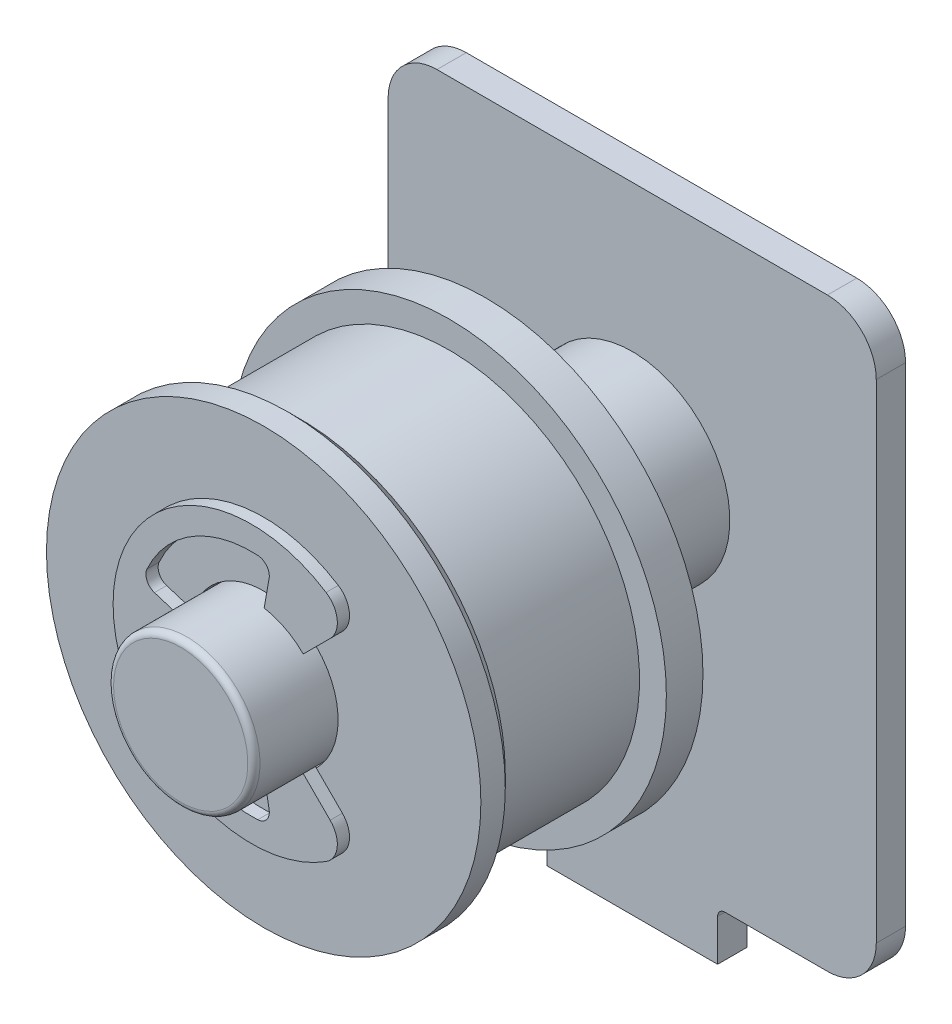
SolidWorks part; units mm, degrees
ref_plane "Plano frontal" through (0, 0, 0) normal (0, 0, 1) x (1, 0, 0)
ref_plane "Plano superior" through (0, 0, 0) normal (0, 1, 0) x (1, 0, 0)
ref_plane "Plano direito" through (0, 0, 0) normal (1, 0, 0) x (0, 0, -1)
sketch "Esboço1" plane through (0, 0, 0) normal (0, 0, 1) x (1, 0, 0)
  line L1 (48.7, 0.625) -> (-48.7, 0.625)
  line L2 (48.7, 0.625) -> (48.7, -0.625)
  line L3 (48.7, -0.625) -> (-48.7, -0.625)
  line L4 (-48.7, 0.625) -> (-48.7, -0.625)
  line L5 (48.7, 0.625) -> (-48.7, -0.625) construction
  line L6 (48.7, -0.625) -> (-48.7, 0.625) construction
  point P0 (0, 0)
  dimension "D1" = 97.4
  dimension "D2" = 1.25
extrude "Ressalto-extrusão1" add sketch "Esboço1" along normal blind 6.2
sketch "Esboço2" plane through (0, -0.625, 0) normal (0, 1, 0) x (1, 0, 0)
  line L0 (48.7, -6.2) -> (48.7, 0) construction
  line L1 (-48.7, 0) -> (48.7, 0)
  line L2 (-48.7, 0) -> (-48.7, -1.25)
  line L3 (-48.7, -1.25) -> (48.7, -1.25)
  line L4 (48.7, 0) -> (48.7, -1.25)
  dimension "D1" = 1.25
extrude "Ressalto-extrusão2" add sketch "Esboço2" along normal blind 40.6 contours L3 L4 L1 L2
fillet "Filete1" radius 1 4 edges at (48.7, 39.975, 0.625) (-48.7, 39.975, 0.625) (48.7, 0, 6.2) (-48.7, 0, 6.2)
sketch "Esboço3" plane through (0, 0, 1.25) normal (0, 0, 1) x (1, 0, 0)
  line L0 (27.7, 34.975) -> (30.7, 34.975) construction
  line L11 (39.7, 33.975) -> (43.7, 33.975)
  line L12 (39.7, 33.975) -> (39.7, 27.975)
  line L13 (39.7, 27.975) -> (43.7, 27.975)
  line L14 (43.7, 33.975) -> (43.7, 27.975)
  line L15 (39.7, 11.975) -> (43.7, 11.975)
  line L16 (39.7, 11.975) -> (39.7, 5.975)
  line L17 (39.7, 5.975) -> (43.7, 5.975)
  line L18 (43.7, 11.975) -> (43.7, 5.975)
  line L19 (-36.7, 12.975) -> (-30.7, 12.975)
  line L20 (-36.7, 12.975) -> (-36.7, 4.975)
  line L21 (-36.7, 4.975) -> (-30.7, 4.975)
  line L22 (-30.7, 12.975) -> (-30.7, 4.975)
  line L23 (27.7, 36.975) -> (30.7, 36.975)
  line L24 (27.7, 32.975) -> (30.7, 32.975)
  line L25 (0, 39.975) -> (0, 2.975) construction
  line L26 (-47.7, 39.975) -> (47.7, 39.975) construction
  line L27 (-47.7, 39.975) -> (47.7, 39.975) construction
  line L28 (-48.7, 38.975) -> (-48.7, 0.625) construction
  line L29 (-36.7, 34.975) -> (-30.7, 34.975)
  line L30 (-36.7, 34.975) -> (-36.7, 26.975)
  line L31 (-36.7, 26.975) -> (-30.7, 26.975)
  line L32 (-30.7, 34.975) -> (-30.7, 26.975)
  line L33 (48.7, 38.975) -> (48.7, 0.625) construction
  line L34 (48.7, 19.8) -> (0, 19.8) construction
  circle A5 centre (-43.7, 4.975) radius 2
  circle A6 centre (0, 4.975) radius 2
  circle A7 centre (38.95, 19.8) radius 2.5
  circle A8 centre (14.7, 19.8) radius 6
  arc A9 (27.7, 36.975) -> (27.7, 32.975) centre (27.7, 34.975) ccw
  arc A10 (30.7, 32.975) -> (30.7, 36.975) centre (30.7, 34.975) ccw
  point P22 (29.2, 34.975)
  point P33 (25.7, 34.975)
  point P34 (32.7, 34.975)
  dimension "D14" = 5
  dimension "D16" = 16
  dimension "D27" = 4
  dimension "D3" = 4
  dimension "D6" = 12
  dimension "D17" = 5
  dimension "D4" = 35
  dimension "D8" = 34
  dimension "D9" = 6
  dimension "D10" = 4
  dimension "D11" = 6
  dimension "D12" = 4
  dimension "D13" = 5
  dimension "D15" = 6
  dimension "D18" = 9.75
  dimension "D19" = 8
  dimension "D20" = 6
  dimension "D21" = 8
  dimension "D22" = 6
  dimension "D23" = 12
  dimension "D24" = 12
  dimension "D25" = 5
  dimension "D26" = 14
  dimension "D28" = 5
  dimension "D29" = 35
  dimension "D30" = 0
  dimension "D31" = 4
  dimension "D32" = 7
  dimension "D33" = 3
  dimension "D34" = 16
extrude "Corte-extrusão1" cut sketch "Esboço3" against normal blind 40.6
sketch "Esboço5" plane through (0, 0, 0) normal (0, 0, -1) x (-1, 0, 0)
  line L0 (-20.7, 19.8) -> (48.7, 19.8) construction
  line L1 (48.7, 38.975) -> (48.7, -0.625) construction
  line L2 (47.7, 39.975) -> (-47.7, 39.975) construction
  line L3 (48.7, 23.975) -> (48.7, 19.8) construction
  circle A0 centre (4.1, 23.975) radius 2
  circle A1 centre (25.7, 19.8) radius 3
  circle A2 centre (-14.7, 19.8) radius 6 construction
  dimension "D1" = 23
  dimension "6" = 6
  dimension "D2" = 4
  dimension "D3" = 16
  dimension "D4" = 44.6
sketch "Esboço6" plane through (0, 0, 0) normal (0, 0, -1) x (-1, 0, 0)
  circle A0 centre (25.7, 19.8) radius 3
  dimension "D1" = 6
extrude "Ressalto-extrusão3" add sketch "Esboço6" against normal blind 22.5
sketch "Esboço7" plane through (0, 0, 0) normal (0, 0, -1) x (-1, 0, 0)
  circle A0 centre (4.1, 23.975) radius 2.25
  dimension "D1" = 4.5
extrude "Ressalto-extrusão4" add sketch "Esboço7" against normal blind 12.3
fillet "Filete2" radius 0.25 2 edges at (-6.35, 23.975, 12.3) (-28.7, 19.8, 22.5)
sketch "Esboço12" plane through (0, 0, 0) normal (0, 0, 1) x (1, 0, 0)
  circle A0 centre (-4.1, 23.975) radius 4
  dimension "D1" = 8
extrude "Ressalto-extrusão7" add sketch "Esboço12" along normal blind 3
sketch "Esboço13" plane through (0, 0, 0) normal (0, 0, -1) x (-1, 0, 0)
  circle A0 centre (25.7, 19.8) radius 4.5
  dimension "D1" = 9
extrude "Ressalto-extrusão8" add sketch "Esboço13" against normal blind 8.1
sketch "Esboço8" plane through (0, 0, 3) normal (0, 0, 1) x (1, 0, 0)
  circle A0 centre (-4.1, 23.975) radius 16.365
  circle A1 centre (-4.1, 23.975) radius 2.3
  dimension "D1" = 32.73
  dimension "D2" = 4.6
extrude "Ressalto-extrusão5" add sketch "Esboço8" along normal blind 4
sketch "Esboço9" plane through (0, 0, 3) normal (0, 0, 1) x (1, 0, 0)
  circle A1 centre (-4.1, 23.975) radius 4
  circle A2 centre (-4.1, 23.975) radius 2.3
  dimension "D1" = 8
extrude "Ressalto-extrusão6" add sketch "Esboço9" along normal blind 8.9
sketch "Esboço10" plane through (0, 0, 7) normal (0, 0, 1) x (1, 0, 0)
  circle A0 centre (-4.1, 23.975) radius 4.9
  circle A1 centre (-4.1, 23.975) radius 13.865
  circle A2 centre (-4.1, 23.975) radius 16.365 construction
  dimension "D1" = 9.8
  dimension "D2" = 2.5
extrude "Corte-extrusão2" cut sketch "Esboço10" against normal blind 1
sketch "Esboço11" plane through (0, 0, 3) normal (0, 0, -1) x (-1, 0, 0)
  circle A1 centre (4.1, 23.975) radius 13.86
  circle A2 centre (4.1, 23.975) radius 4.9
extrude "Corte-extrusão3" cut sketch "Esboço11" against normal blind 1
sketch "Esboço14" plane through (0, 0, 8.1) normal (0, 0, 1) x (1, 0, 0)
  circle A0 centre (-25.7, 19.8) radius 18.34
  circle A1 centre (-25.7, 19.8) radius 3.1
  circle A2 centre (-25.7, 19.8) radius 3 construction
  dimension "D1" = 36.68
  dimension "D2" = 0.1
extrude "Ressalto-extrusão9" add sketch "Esboço14" along normal blind 4
sketch "Esboço15" plane through (0, 0, 8.1) normal (0, 0, 1) x (1, 0, 0)
  circle A0 centre (-25.7, 19.8) radius 7.8
  circle A1 centre (-25.7, 19.8) radius 3.1
  dimension "D1" = 15.6
extrude "Ressalto-extrusão10" add sketch "Esboço15" along normal blind 11.6
sketch "Esboço16" plane through (0, 0, 19.7) normal (0, 0, 1) x (1, 0, 0)
  circle A0 centre (-25.7, 19.8) radius 3.1
  circle A1 centre (-25.7, 19.8) radius 8.9
  dimension "D1" = 17.8
extrude "Ressalto-extrusão11" add sketch "Esboço16" against normal blind 1.5
chamfer "Chanfro1" distance 0.5 angle 45 1 edges at (-16.8, 19.8, 18.2)
sketch "Esboço17" plane through (0, 0, 19.7) normal (0, 0, 1) x (1, 0, 0)
  circle A0 centre (-25.7, 19.8) radius 3.1
  circle A1 centre (-25.7, 19.8) radius 3.5
  dimension "D1" = 7
extrude "Ressalto-extrusão12" add sketch "Esboço17" along normal blind 0.5
sketch "Esboço18" plane through (0, 0, 12.1) normal (0, 0, 1) x (1, 0, 0)
  circle A0 centre (-25.7, 19.8) radius 15.84
  circle A1 centre (-25.7, 19.8) radius 8.9
  circle A2 centre (-25.7, 19.8) radius 18.34 construction
  dimension "D1" = 2.5
  dimension "D2" = 17.8
extrude "Corte-extrusão4" cut sketch "Esboço18" against normal blind 1
sketch "Esboço19" plane through (0, 0, 8.1) normal (0, 0, -1) x (-1, 0, 0)
  circle A0 centre (25.7, 19.8) radius 8.9
  circle A1 centre (25.7, 19.8) radius 15.825
extrude "Corte-extrusão5" cut sketch "Esboço19" against normal blind 1
sketch "Esboço20" plane through (0, 0, 20.2) normal (0, 0, 1) x (1, 0, 0)
  line L0 (-28.3227, 20.6269) -> (-29.675, 21.0533)
  line L3 (-23.7555, 21.7445) -> (-22.4747, 23.0253)
  line L4 (-25.2225, 22.5082) -> (-24.9763, 23.9046)
  line L5 (-23.7555, 17.8555) -> (-22.4747, 16.5747)
  line L6 (-25.2225, 17.0918) -> (-24.9763, 15.6954)
  line L7 (-28.3227, 18.9731) -> (-29.675, 18.5467)
  arc A0 (-22.6425, 24.5746) -> (-22.6425, 15.0254) centre (-25.7, 19.8) ccw
  arc A1 (-25.4411, 24.4906) -> (-29.9802, 21.7362) centre (-25.7, 19.8) ccw
  arc A2 (-28.3227, 20.6269) -> (-28.3227, 18.9731) centre (-25.7, 19.8) ccw
  arc A3 (-23.7555, 21.7445) -> (-25.2225, 22.5082) centre (-25.7, 19.8) ccw
  arc A4 (-25.2225, 17.0918) -> (-23.7555, 17.8555) centre (-25.7, 19.8) ccw
  arc A5 (-29.9802, 17.8638) -> (-25.4411, 15.1094) centre (-25.7, 19.8) ccw
  arc A6 (-22.4747, 16.5747) -> (-22.6425, 15.0254) centre (-23.1818, 15.8675) cw
  arc A7 (-22.4747, 23.0253) -> (-22.6425, 24.5746) centre (-23.1818, 23.7325) ccw
  arc A8 (-25.4411, 15.1094) -> (-24.9763, 15.6954) centre (-25.4687, 15.6086) ccw
  arc A9 (-25.4411, 24.4906) -> (-24.9763, 23.9046) centre (-25.4687, 23.9914) cw
  arc A10 (-29.9802, 17.8638) -> (-29.675, 18.5467) centre (-29.5246, 18.0698) cw
  arc A11 (-29.9802, 21.7362) -> (-29.675, 21.0533) centre (-29.5246, 21.5302) ccw
  dimension "D2" = 1
  dimension "D3" = 0.5
  dimension "D1" = 35
  dimension "D4" = 35
  dimension "D5" = 35
extrude "Ressalto-extrusão13" add sketch "Esboço20" along normal blind 0.5
sketch "Esboço21" plane through (0, 0, 0) normal (0, 0, -1) x (-1, 0, 0)
  line L0 (-29.3939, 34.975) -> (0, 4.975) construction
  line L1 (3.3061, 4.975) -> (-3.6939, 4.975) construction
  line L2 (3.5952, 5.1615) -> (2.7796, 20.8817)
  line L3 (-13.4337, 37.4293) -> (-29.134, 38.5656)
  line L4 (0, 1.375) -> (-4.8727, 1.375)
  line L5 (-32.9939, 34.975) -> (-32.9939, 30.076)
  line L6 (-32.9939, 30.076) -> (-30.4878, 27.5182)
  line L7 (-7.4776, 4.0335) -> (-4.8727, 1.375)
  circle A2 centre (0, 4.975) radius 1.75
  circle A3 centre (-29.3939, 34.975) radius 1.75
  arc A4 (-30.4878, 27.5182) -> (-7.4776, 4.0335) centre (-14.6969, 19.975) ccw
  arc A5 (0, 1.375) -> (3.5952, 5.1615) centre (0, 4.975) ccw
  arc A7 (-29.134, 38.5656) -> (-32.9939, 34.975) centre (-29.3939, 34.975) ccw
  arc A9 (2.7796, 20.8817) -> (-13.4337, 37.4293) centre (-14.6969, 19.975) ccw
  dimension "D2" = 3.5
  dimension "D3" = 3.5
  dimension "D4" = 35
  dimension "D5" = 7.2
  dimension "D1" = 42
  dimension "D7" = 6
extrude "Ressalto-extrusão14" add sketch "Esboço21" along normal blind 0.92
sketch "Esboço23" plane through (0, 0, 0) normal (0, 0, 1) x (1, 0, 0)
  circle A0 centre (14.7, 19.8) radius 17.675
extrude "Ressalto-extrusão15" add sketch "Esboço23" against normal blind 15
fillet "Filete4" radius 1 1 edges at (32.375, 19.8, -15)
sketch "Esboço24" plane through (0, 0, -0.92) normal (0, 0, -1) x (-1, 0, 0)
  circle A0 centre (0, 4.975) radius 1.75
  circle A1 centre (0, 4.975) radius 2.05
  circle A2 centre (-29.3939, 34.975) radius 1.75
  circle A3 centre (-29.3939, 34.975) radius 2.05
  dimension "D1" = 0.3
  dimension "D2" = 0.3
extrude "Ressalto-extrusão16" add sketch "Esboço24" along normal blind 1
sketch "Esboço25" plane through (0, 0, -15) normal (0, 0, -1) x (-1, 0, 0)
  circle A0 centre (-14.7, 19.8) radius 2.5
  dimension "D1" = 5
extrude "Ressalto-extrusão17" add sketch "Esboço25" along normal blind 0.1
sketch "Esboço26" plane through (0, 0, -15.1) normal (0, 0, -1) x (-1, 0, 0)
  circle A0 centre (-14.7, 19.8) radius 1
  dimension "D1" = 2
extrude "Ressalto-extrusão18" add sketch "Esboço26" along normal blind 0.5
fillet "Filete6" radius 0.1 1 edges at (12.2, 19.8, -15.1)
sketch "Esboço27" plane through (0, 0, -15) normal (0, 0, 1) x (1, 0, 0)
  circle A0 centre (14.7, 19.8) radius 4.99
  dimension "D1" = 9.98
extrude "Ressalto-extrusão19" add sketch "Esboço27" along normal blind 16.57
sketch "Esboço28" plane through (0, 0, -15.6) normal (0, 0, -1) x (-1, 0, 0)
  circle A0 centre (-14.7, 19.8) radius 1
extrude "Ressalto-extrusão20" add sketch "Esboço28" against normal blind 25
fillet "Filete5" radius 0.25 2 edges at (13.7, 19.8, -15.6) (13.7, 19.8, 9.4)
ref_plane "Plano2" through (0, 0, 9.15) normal (0, 0, 1) x (1, 0, 0)
sketch "Esboço29" plane through (0, 0, 9.15) normal (0, 0, 1) x (1, 0, 0)
  circle A0 centre (14.7, 19.8) radius 3.59
  dimension "D1" = 7.18
extrude "Ressalto-extrusão21" add sketch "Esboço29" against normal blind 6
sketch "Esboço30" plane through (0, 0, 1.25) normal (0, 0, 1) x (1, 0, 0)
  circle A0 centre (0, 4.975) radius 2.7
  circle A1 centre (29.3939, 34.975) radius 2.7
  dimension "D1" = 5.4
  dimension "D2" = 5.4
extrude "Ressalto-extrusão22" add sketch "Esboço30" along normal blind 2
fillet "Filete7" radius 1.4 2 edges at (2.7, 4.975, 3.25) (32.0939, 34.975, 3.25)
sketch "Esboço31" plane through (0, 0, 3.25) normal (0, 0, 1) x (1, 0, 0)
  line L1 (29.0939, 37.175) -> (29.6939, 37.175)
  line L2 (28.8939, 36.975) -> (28.8939, 35.975)
  line L3 (29.0939, 32.775) -> (29.6939, 32.775)
  line L4 (29.8939, 36.975) -> (29.8939, 35.975)
  line L7 (31.3939, 35.475) -> (30.3939, 35.475)
  line L8 (31.5939, 35.275) -> (31.5939, 34.675)
  line L9 (31.3939, 34.475) -> (30.3939, 34.475)
  line L10 (27.1939, 35.275) -> (27.1939, 34.675)
  line L15 (28.8939, 33.975) -> (28.8939, 32.975)
  line L17 (29.8939, 33.975) -> (29.8939, 32.975)
  line L18 (28.3939, 35.475) -> (27.3939, 35.475)
  line L19 (28.3939, 34.475) -> (27.3939, 34.475)
  line L42 (-0.1421, 7.325) -> (0.4579, 7.325)
  line L43 (-0.3421, 7.125) -> (-0.3421, 6.125)
  line L44 (-0.1421, 2.925) -> (0.4579, 2.925)
  line L45 (0.6579, 7.125) -> (0.6579, 6.125)
  line L46 (2.1579, 5.625) -> (1.1579, 5.625)
  line L47 (2.3579, 5.425) -> (2.3579, 4.825)
  line L48 (2.1579, 4.625) -> (1.1579, 4.625)
  line L49 (-2.0421, 5.425) -> (-2.0421, 4.825)
  line L50 (-0.3421, 4.125) -> (-0.3421, 3.125)
  line L51 (0.6579, 4.125) -> (0.6579, 3.125)
  line L52 (-0.8421, 5.625) -> (-1.8421, 5.625)
  line L53 (-0.8421, 4.625) -> (-1.8421, 4.625)
  arc A0 (29.8939, 33.975) -> (30.3939, 34.475) centre (30.3939, 33.975) cw
  arc A1 (28.8939, 33.975) -> (28.3939, 34.475) centre (28.3939, 33.975) ccw
  arc A2 (29.8939, 35.975) -> (30.3939, 35.475) centre (30.3939, 35.975) ccw
  arc A3 (28.8939, 35.975) -> (28.3939, 35.475) centre (28.3939, 35.975) cw
  arc A4 (28.8939, 32.975) -> (29.0939, 32.775) centre (29.0939, 32.975) ccw
  arc A5 (29.6939, 32.775) -> (29.8939, 32.975) centre (29.6939, 32.975) ccw
  arc A6 (31.5939, 34.675) -> (31.3939, 34.475) centre (31.3939, 34.675) cw
  arc A7 (31.3939, 35.475) -> (31.5939, 35.275) centre (31.3939, 35.275) cw
  arc A8 (29.6939, 37.175) -> (29.8939, 36.975) centre (29.6939, 36.975) cw
  arc A9 (29.0939, 37.175) -> (28.8939, 36.975) centre (29.0939, 36.975) ccw
  arc A10 (27.3939, 35.475) -> (27.1939, 35.275) centre (27.3939, 35.275) ccw
  arc A11 (27.3939, 34.475) -> (27.1939, 34.675) centre (27.3939, 34.675) cw
  circle A24 centre (29.3939, 34.975) radius 1.3 construction
  arc A37 (0.6579, 4.125) -> (1.1579, 4.625) centre (1.1579, 4.125) cw
  arc A38 (-0.3421, 4.125) -> (-0.8421, 4.625) centre (-0.8421, 4.125) ccw
  arc A39 (0.6579, 6.125) -> (1.1579, 5.625) centre (1.1579, 6.125) ccw
  arc A40 (-0.3421, 6.125) -> (-0.8421, 5.625) centre (-0.8421, 6.125) cw
  arc A41 (-0.3421, 3.125) -> (-0.1421, 2.925) centre (-0.1421, 3.125) ccw
  arc A42 (0.4579, 2.925) -> (0.6579, 3.125) centre (0.4579, 3.125) ccw
  arc A43 (2.3579, 4.825) -> (2.1579, 4.625) centre (2.1579, 4.825) cw
  arc A44 (2.1579, 5.625) -> (2.3579, 5.425) centre (2.1579, 5.425) cw
  arc A45 (0.4579, 7.325) -> (0.6579, 7.125) centre (0.4579, 7.125) cw
  arc A46 (-0.1421, 7.325) -> (-0.3421, 7.125) centre (-0.1421, 7.125) ccw
  arc A47 (-1.8421, 5.625) -> (-2.0421, 5.425) centre (-1.8421, 5.425) ccw
  arc A48 (-1.8421, 4.625) -> (-2.0421, 4.825) centre (-1.8421, 4.825) cw
  point P0 (0, 4.975)
  point P6 (29.3939, 34.975)
  point P19 (28.8939, 34.475)
  point P24 (28.8939, 35.475)
  point P27 (28.8939, 32.775)
  point P30 (29.8939, 32.775)
  point P33 (31.5939, 34.475)
  point P36 (31.5939, 35.475)
  point P39 (29.8939, 37.175)
  point P44 (27.1939, 35.475)
  point P128 (0.1579, 5.125)
  point P133 (0.1579, 5.125)
  dimension "D5" = 0.5
  dimension "D6" = 0.2
  dimension "D9" = 0.5
  dimension "D10" = 0.2
  dimension "D1" = 4.4
  dimension "D2" = 4.4
  dimension "D3" = 1
  dimension "D4" = 1
extrude "Corte-extrusão6" cut sketch "Esboço31" against normal blind 1.4
sketch "Esboço32" plane through (0, 0, 1.25) normal (0, 0, -1) x (-1, 0, 0)
  circle A0 centre (0, 4.975) radius 1.75
  circle A1 centre (-29.3939, 34.975) radius 1.75
extrude "Ressalto-extrusão23" add sketch "Esboço32" along normal blind 7.8
chamfer "Chanfro2" distance 1 angle 25 2 edges at (-1.75, 4.975, -6.55) (27.6439, 34.975, -6.55) first distance on face at (-1.75, 4.975, -1.92) first distance on face at (27.6439, 34.975, -1.92)
sketch "Esboço33" plane through (0, 0, -0.92) normal (0, 0, -1) x (-1, 0, 0)
  line L1 (3.2243, 12.8461) -> (4.2922, 22.7889)
  line L2 (4.2922, 22.7889) -> (2.6901, 22.961)
  line L3 (3.2243, 12.8461) -> (1.6222, 13.0182)
  arc A4 (1.6222, 13.0182) -> (2.6901, 22.961) centre (-14.7, 19.8) ccw
  arc A7 (1.6222, 13.0182) -> (2.6901, 22.961) centre (-14.7, 19.8) ccw
  arc M4 (2.9127, 18.3164) -> (-7.2301, 3.781) centre (-14.7, 19.8) cw
  line M8 (3.5952, 5.1615) -> (2.9127, 18.3164)
  dimension "D1" = 10
  dimension "D2" = 90
extrude "Ressalto-extrusão24" add sketch "Esboço33" along normal blind 10 contours A4 L3 L1 L2 M8 | L3 M8 M4 region at (-3.4256, 19.3944, -0.92) region at (-2.6269, 14.5261, -0.92)
sketch "Esboço34" plane through (-1.8235, -0.1959, 0) normal (-0.9943, -0.1068, 0) x (0, 0, 1)
  line L0 (-5.92, 23.117) -> (-5.92, 13.117) construction
  line L1 (-10.92, 23.117) -> (-0.92, 23.117) construction
  line L2 (-10.92, 13.117) -> (-0.92, 13.117) construction
  circle A0 centre (-5.92, 18.117) radius 2
  dimension "D1" = 4
extrude "Ressalto-extrusão25" add sketch "Esboço34" along normal blind 5
sketch "Esboço35" plane through (0, 0, 12.1) normal (0, 0, 1) x (1, 0, 0)
  line L0 (-48.7, 38.975) -> (-48.7, 0.625) construction
  circle A0 centre (-398.7, 19.8) radius 7.8
  point P2 (-25.7, 19.8)
  dimension "D1" = 15.6
  dimension "D2" = 350
  dimension "D3" = 0
extrude "Ressalto-extrusão26" add sketch "Esboço35" along normal blind 7.6 separate body
sketch "Esboço37" plane through (0, 0, 19.7) normal (0, 0, 1) x (1, 0, 0)
  circle A0 centre (-398.7, 19.8) radius 8.9
  dimension "D1" = 17.8
extrude "Ressalto-extrusão27" add sketch "Esboço37" against normal blind 1.5
chamfer "Chanfro3" distance 0.5 angle 45 1 edges at (-389.8, 19.8, 18.2)
sketch "Esboço38" plane through (0, 0, 12.1) normal (0, 0, -1) x (-1, 0, 0)
  circle A0 centre (398.7, 19.8) radius 8.9
extrude "Ressalto-extrusão28" add sketch "Esboço38" along normal blind 1.5
sketch "Esboço39" plane through (0, 0, 19.7) normal (0, 0, 1) x (1, 0, 0)
  circle A0 centre (-398.7, 19.8) radius 3.05
  dimension "D1" = 6.1
extrude "Corte-extrusão7" cut sketch "Esboço39" against normal blind 35.5 and the other way blind 16
sketch "Esboço40" plane through (0, 0, 10.6) normal (0, 0, -1) x (-1, 0, 0)
  circle A0 centre (398.7, 19.8) radius 4
  dimension "D1" = 8
extrude "Ressalto-extrusão29" add sketch "Esboço40" along normal blind 6
sketch "Esboço41" plane through (0, 0, 4.6) normal (0, 0, -1) x (-1, 0, 0)
  circle A0 centre (398.7, 19.8) radius 3
  dimension "D1" = 6
extrude "Ressalto-extrusão30" add sketch "Esboço41" against normal blind 18.5
fillet "Filete8" radius 0.25 1 edges at (-401.7, 19.8, 23.1)
sketch "Esboço42" plane through (0, 0, 19.7) normal (0, 0, 1) x (1, 0, 0)
  line L6 (-401.3227, 20.6269) -> (-402.675, 21.0533)
  line L7 (-396.7555, 21.7445) -> (-395.4747, 23.0253)
  line L8 (-398.2225, 22.5082) -> (-397.9763, 23.9046)
  line L9 (-396.7555, 17.8555) -> (-395.4747, 16.5747)
  line L10 (-398.2225, 17.0918) -> (-397.9763, 15.6954)
  line L11 (-401.3227, 18.9731) -> (-402.675, 18.5467)
  arc A12 (-395.6425, 24.5746) -> (-395.6425, 15.0254) centre (-398.7, 19.8) ccw
  arc A13 (-398.4411, 24.4906) -> (-402.9802, 21.7362) centre (-398.7, 19.8) ccw
  arc A14 (-401.3227, 20.6269) -> (-401.3227, 18.9731) centre (-398.7, 19.8) ccw
  arc A15 (-396.7555, 21.7445) -> (-398.2225, 22.5082) centre (-398.7, 19.8) ccw
  arc A16 (-398.2225, 17.0918) -> (-396.7555, 17.8555) centre (-398.7, 19.8) ccw
  arc A17 (-402.9802, 17.8638) -> (-398.4411, 15.1094) centre (-398.7, 19.8) ccw
  arc A18 (-395.4747, 16.5747) -> (-395.6425, 15.0254) centre (-396.1818, 15.8675) cw
  arc A19 (-395.4747, 23.0253) -> (-395.6425, 24.5746) centre (-396.1818, 23.7325) ccw
  arc A20 (-398.4411, 15.1094) -> (-397.9763, 15.6954) centre (-398.4687, 15.6086) ccw
  arc A21 (-398.4411, 24.4906) -> (-397.9763, 23.9046) centre (-398.4687, 23.9914) cw
  arc A22 (-402.9802, 17.8638) -> (-402.675, 18.5467) centre (-402.5246, 18.0698) cw
  arc A23 (-402.9802, 21.7362) -> (-402.675, 21.0533) centre (-402.5246, 21.5302) ccw
  point P0 (-398.7, 19.8)
  dimension "D4" = 1
  dimension "D5" = 0.5
  dimension "D1" = 35
  dimension "D2" = 35
  dimension "D3" = 35
extrude "Ressalto-extrusão31" add sketch "Esboço42" along normal blind 0.5
sketch "Esboço43" plane through (0, 0, 4.6) normal (0, 0, -1) x (-1, 0, 0)
  line L0 (402.2, 5.8) -> (402.2, 3.8)
  line L1 (408.7, 29.8) -> (388.7, 29.8)
  line L2 (408.7, 29.8) -> (408.7, 5.8)
  line L3 (408.7, 5.8) -> (402.2, 5.8)
  line L4 (388.7, 29.8) -> (388.7, 5.8)
  line L5 (395.2, 5.8) -> (388.7, 5.8)
  line L6 (408.7, 19.8) -> (388.7, 19.8) construction
  line L9 (395.2, 3.8) -> (402.2, 3.8)
  line L11 (398.7, 29.8) -> (398.7, 19.8) construction
  line L14 (395.2, 5.8) -> (395.2, 3.8)
  point P0 (398.7, 19.8)
  dimension "D1" = 20
  dimension "D2" = 24
  dimension "D4" = 7
  dimension "D5" = 26
extrude "Ressalto-extrusão32" add sketch "Esboço43" along normal blind 1.2 contours L1 L4 L5 L14 L9 L0 L3 L2
fillet "Filete9" radius 2 4 edges at (-408.7, 5.8, 4) (-388.7, 5.8, 4) (-388.7, 29.8, 4) (-408.7, 29.8, 4)
fillet "Filete10" radius 0.3 2 edges at (-402.2, 5.8, 4) (-395.2, 5.8, 4)
ref_plane "Plano3" through (0, 0, 13.1) normal (0, 0, 1) x (1, 0, 0)
sketch "Esboço45" plane through (0, 0, 3.4) normal (0, 0, -1) x (-1, 0, 0)
  line L0 (398.7, 3.8) -> (398.7, 29.8) construction
  line L1 (395.2, 3.8) -> (402.2, 3.8) construction
  line L2 (406.7, 29.8) -> (390.7, 29.8) construction
  line L4 (388.7, 27.8) -> (388.7, 7.8) construction
  line L5 (388.7, 17.8) -> (408.7, 17.8) construction
  line L6 (408.7, 27.8) -> (408.7, 7.8) construction
fillet "Filete11" radius 0.5 1 edges at (0, -0.625, 0)
fillet "Filete12" radius 0.25 1 edges at (0, 0.625, 1.25)
delete or keep bodies "Corpo-Excluir/Manter 1" type delete bodies bodies 131
